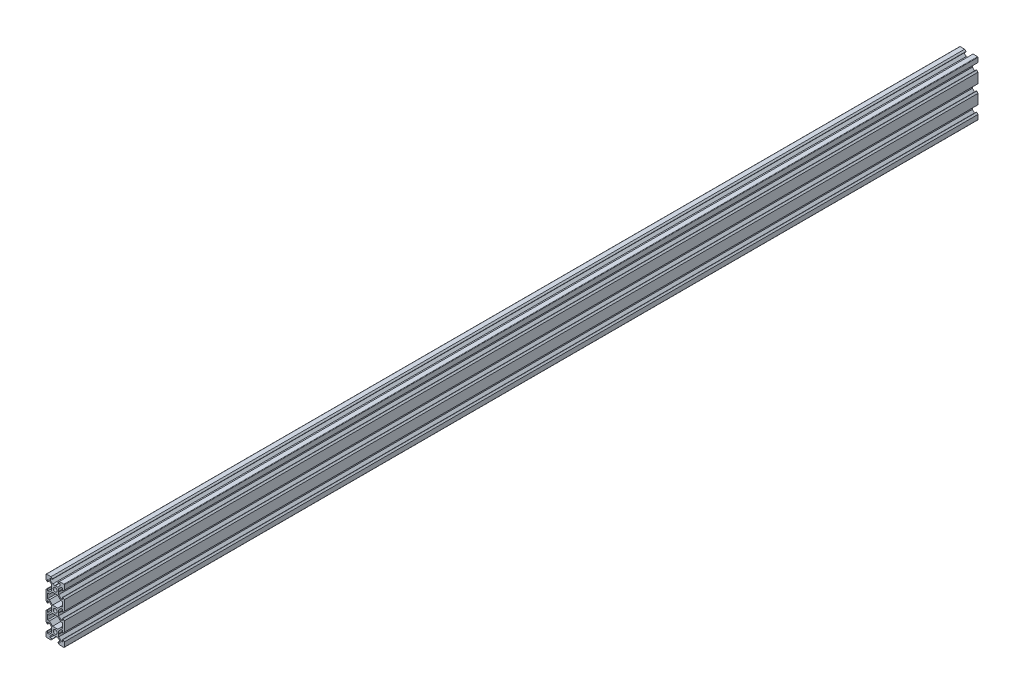
SolidWorks part; units mm, degrees
material "6061-T6 (SS)"
ref_plane "Front Plane" through (0, 0, 0) normal (0, 0, 1) x (1, 0, 0)
ref_plane "Top Plane" through (0, 0, 0) normal (0, 1, 0) x (1, 0, 0)
ref_plane "Right Plane" through (0, 0, 0) normal (1, 0, 0) x (0, 0, -1)
sketch "Sketch1" plane through (0, 0, 0) normal (0, 0, 1) x (1, 0, 0)
  line L0 (0, 0) -> (10, 0) construction
  line L1 (9.5, -30) -> (-9.5, -30)
  line L2 (10, -29.5) -> (10, 29.5)
  line L3 (9.5, 30) -> (-9.5, 30)
  line L4 (-10, -29.5) -> (-10, 29.5)
  line L5 (10, -30) -> (-10, 30) construction
  line L6 (10, 30) -> (-10, -30) construction
  circle A0 centre (0, 20) radius 2.1
  circle A1 centre (0, 0) radius 2.1
  circle A2 centre (0, -20) radius 2.1
  arc A3 (-9.5, -30) -> (-10, -29.5) centre (-9.5, -29.5) cw
  arc A4 (9.5, -30) -> (10, -29.5) centre (9.5, -29.5) ccw
  arc A5 (10, 29.5) -> (9.5, 30) centre (9.5, 29.5) ccw
  arc A6 (-9.5, 30) -> (-10, 29.5) centre (-9.5, 29.5) ccw
  point P0 (0, 0)
  line B0 (0, 20) -> (0, 30) construction
  line B1 (0, 23.69) -> (-0.21, 23.9)
  line B2 (-0.21, 23.9) -> (-2.8393, 23.9)
  line B3 (-2.8393, 23.9) -> (-5.5, 26.5607)
  line B4 (-5.5, 26.5607) -> (-5.5, 28.2)
  line B5 (-5.5, 28.2) -> (-3.125, 28.2)
  line B6 (-3.125, 28.2) -> (-3.125, 28.545)
  line B7 (-3.125, 28.545) -> (-4.58, 30)
  line B8 (-4.58, 30) -> (4.58, 30)
  line B9 (0, 20) -> (-5.9132, 25.9132) construction
  line B10 (3.125, 28.545) -> (4.58, 30)
  line B11 (3.125, 28.2) -> (3.125, 28.545)
  line B12 (5.5, 28.2) -> (3.125, 28.2)
  line B13 (5.5, 26.5607) -> (5.5, 28.2)
  line B14 (2.8393, 23.9) -> (5.5, 26.5607)
  line B15 (0.21, 23.9) -> (2.8393, 23.9)
  line B16 (0, 23.69) -> (0.21, 23.9)
  line B17 (0, 20) -> (-10, 20) construction
  line B18 (-3.69, 20) -> (-3.9, 19.79)
  line B19 (-3.9, 19.79) -> (-3.9, 17.1607)
  line B20 (-3.9, 17.1607) -> (-6.5607, 14.5)
  line B21 (-6.5607, 14.5) -> (-8.2, 14.5)
  line B22 (-8.2, 14.5) -> (-8.2, 16.875)
  line B23 (-8.2, 16.875) -> (-8.545, 16.875)
  line B24 (-8.545, 16.875) -> (-10, 15.42)
  line B25 (-10, 15.42) -> (-10, 24.58)
  line B26 (0, 20) -> (-5.9132, 14.0868) construction
  line B27 (-8.545, 23.125) -> (-10, 24.58)
  line B28 (-8.2, 23.125) -> (-8.545, 23.125)
  line B29 (-8.2, 25.5) -> (-8.2, 23.125)
  line B30 (-6.5607, 25.5) -> (-8.2, 25.5)
  line B31 (-3.9, 22.8393) -> (-6.5607, 25.5)
  line B32 (-3.9, 20.21) -> (-3.9, 22.8393)
  line B33 (-3.69, 20) -> (-3.9, 20.21)
  line B34 (0, 0) -> (-10, 0) construction
  line B35 (-3.69, 0) -> (-3.9, -0.21)
  line B36 (-3.9, -0.21) -> (-3.9, -2.8393)
  line B37 (-3.9, -2.8393) -> (-6.5607, -5.5)
  line B38 (-6.5607, -5.5) -> (-8.2, -5.5)
  line B39 (-8.2, -5.5) -> (-8.2, -3.125)
  line B40 (-8.2, -3.125) -> (-8.545, -3.125)
  line B41 (-8.545, -3.125) -> (-10, -4.58)
  line B42 (-10, -4.58) -> (-10, 4.58)
  line B43 (0, 0) -> (-5.9132, -5.9132) construction
  line B44 (-8.545, 3.125) -> (-10, 4.58)
  line B45 (-8.2, 3.125) -> (-8.545, 3.125)
  line B46 (-8.2, 5.5) -> (-8.2, 3.125)
  line B47 (-6.5607, 5.5) -> (-8.2, 5.5)
  line B48 (-3.9, 2.8393) -> (-6.5607, 5.5)
  line B49 (-3.9, 0.21) -> (-3.9, 2.8393)
  line B50 (-3.69, 0) -> (-3.9, 0.21)
  line B51 (0, -20) -> (-10, -20) construction
  line B52 (-3.69, -20) -> (-3.9, -20.21)
  line B53 (-3.9, -20.21) -> (-3.9, -22.8393)
  line B54 (-3.9, -22.8393) -> (-6.5607, -25.5)
  line B55 (-6.5607, -25.5) -> (-8.2, -25.5)
  line B56 (-8.2, -25.5) -> (-8.2, -23.125)
  line B57 (-8.2, -23.125) -> (-8.545, -23.125)
  line B58 (-8.545, -23.125) -> (-10, -24.58)
  line B59 (-10, -24.58) -> (-10, -15.42)
  line B60 (0, -20) -> (-5.9132, -25.9132) construction
  line B61 (-8.545, -16.875) -> (-10, -15.42)
  line B62 (-8.2, -16.875) -> (-8.545, -16.875)
  line B63 (-8.2, -14.5) -> (-8.2, -16.875)
  line B64 (-6.5607, -14.5) -> (-8.2, -14.5)
  line B65 (-3.9, -17.1607) -> (-6.5607, -14.5)
  line B66 (-3.9, -19.79) -> (-3.9, -17.1607)
  line B67 (-3.69, -20) -> (-3.9, -19.79)
  line B68 (0, -20) -> (0, -30) construction
  line B69 (0, -23.69) -> (0.21, -23.9)
  line B70 (0.21, -23.9) -> (2.8393, -23.9)
  line B71 (2.8393, -23.9) -> (5.5, -26.5607)
  line B72 (5.5, -26.5607) -> (5.5, -28.2)
  line B73 (5.5, -28.2) -> (3.125, -28.2)
  line B74 (3.125, -28.2) -> (3.125, -28.545)
  line B75 (3.125, -28.545) -> (4.58, -30)
  line B76 (4.58, -30) -> (-4.58, -30)
  line B77 (0, -20) -> (5.9132, -25.9132) construction
  line B78 (-3.125, -28.545) -> (-4.58, -30)
  line B79 (-3.125, -28.2) -> (-3.125, -28.545)
  line B80 (-5.5, -28.2) -> (-3.125, -28.2)
  line B81 (-5.5, -26.5607) -> (-5.5, -28.2)
  line B82 (-2.8393, -23.9) -> (-5.5, -26.5607)
  line B83 (-0.21, -23.9) -> (-2.8393, -23.9)
  line B84 (0, -23.69) -> (-0.21, -23.9)
  line B85 (0, -20) -> (10, -20) construction
  line B86 (3.69, -20) -> (3.9, -19.79)
  line B87 (3.9, -19.79) -> (3.9, -17.1607)
  line B88 (3.9, -17.1607) -> (6.5607, -14.5)
  line B89 (6.5607, -14.5) -> (8.2, -14.5)
  line B90 (8.2, -14.5) -> (8.2, -16.875)
  line B91 (8.2, -16.875) -> (8.545, -16.875)
  line B92 (8.545, -16.875) -> (10, -15.42)
  line B93 (10, -15.42) -> (10, -24.58)
  line B94 (0, -20) -> (5.9132, -14.0868) construction
  line B95 (8.545, -23.125) -> (10, -24.58)
  line B96 (8.2, -23.125) -> (8.545, -23.125)
  line B97 (8.2, -25.5) -> (8.2, -23.125)
  line B98 (6.5607, -25.5) -> (8.2, -25.5)
  line B99 (3.9, -22.8393) -> (6.5607, -25.5)
  line B100 (3.9, -20.21) -> (3.9, -22.8393)
  line B101 (3.69, -20) -> (3.9, -20.21)
  line B102 (0, 0) -> (10, 0) construction
  line B103 (3.69, 0) -> (3.9, 0.21)
  line B104 (3.9, 0.21) -> (3.9, 2.8393)
  line B105 (3.9, 2.8393) -> (6.5607, 5.5)
  line B106 (6.5607, 5.5) -> (8.2, 5.5)
  line B107 (8.2, 5.5) -> (8.2, 3.125)
  line B108 (8.2, 3.125) -> (8.545, 3.125)
  line B109 (8.545, 3.125) -> (10, 4.58)
  line B110 (10, 4.58) -> (10, -4.58)
  line B111 (0, 0) -> (5.9132, 5.9132) construction
  line B112 (8.545, -3.125) -> (10, -4.58)
  line B113 (8.2, -3.125) -> (8.545, -3.125)
  line B114 (8.2, -5.5) -> (8.2, -3.125)
  line B115 (6.5607, -5.5) -> (8.2, -5.5)
  line B116 (3.9, -2.8393) -> (6.5607, -5.5)
  line B117 (3.9, -0.21) -> (3.9, -2.8393)
  line B118 (3.69, 0) -> (3.9, -0.21)
  line B119 (0, 20) -> (10, 20) construction
  line B120 (3.69, 20) -> (3.9, 20.21)
  line B121 (3.9, 20.21) -> (3.9, 22.8393)
  line B122 (3.9, 22.8393) -> (6.5607, 25.5)
  line B123 (6.5607, 25.5) -> (8.2, 25.5)
  line B124 (8.2, 25.5) -> (8.2, 23.125)
  line B125 (8.2, 23.125) -> (8.545, 23.125)
  line B126 (8.545, 23.125) -> (10, 24.58)
  line B127 (10, 24.58) -> (10, 15.42)
  line B128 (0, 20) -> (5.9132, 25.9132) construction
  line B129 (8.545, 16.875) -> (10, 15.42)
  line B130 (8.2, 16.875) -> (8.545, 16.875)
  line B131 (8.2, 14.5) -> (8.2, 16.875)
  line B132 (6.5607, 14.5) -> (8.2, 14.5)
  line B133 (3.9, 17.1607) -> (6.5607, 14.5)
  line B134 (3.9, 19.79) -> (3.9, 17.1607)
  line B135 (3.69, 20) -> (3.9, 19.79)
  line B136 (-8.2, 7.3) -> (-8.2, 12.7)
  line B137 (-8.2, 12.7) -> (-6.2393, 12.7)
  line B138 (-6.2393, 12.7) -> (-2.8393, 16.1)
  line B139 (-2.8393, 16.1) -> (2.8393, 16.1)
  line B140 (0, 16.1) -> (0, 10) construction
  line B141 (0, 10) -> (-8.2, 10) construction
  line B142 (6.2393, 12.7) -> (2.8393, 16.1)
  line B143 (8.2, 12.7) -> (6.2393, 12.7)
  line B144 (8.2, 7.3) -> (8.2, 12.7)
  line B145 (8.2, 7.3) -> (6.2393, 7.3)
  line B146 (6.2393, 7.3) -> (2.8393, 3.9)
  line B147 (-2.8393, 3.9) -> (2.8393, 3.9)
  line B148 (-6.2393, 7.3) -> (-2.8393, 3.9)
  line B149 (-8.2, 7.3) -> (-6.2393, 7.3)
  line B150 (0, 16.1) -> (0, 20) construction
  line B151 (0, 20) -> (-5.0927, 14.9073) construction
  line B152 (-8.2, -12.7) -> (-8.2, -7.3)
  line B153 (-8.2, -7.3) -> (-6.2393, -7.3)
  line B154 (-6.2393, -7.3) -> (-2.8393, -3.9)
  line B155 (-2.8393, -3.9) -> (2.8393, -3.9)
  line B156 (0, -3.9) -> (0, -10) construction
  line B157 (0, -10) -> (-8.2, -10) construction
  line B158 (6.2393, -7.3) -> (2.8393, -3.9)
  line B159 (8.2, -7.3) -> (6.2393, -7.3)
  line B160 (8.2, -12.7) -> (8.2, -7.3)
  line B161 (8.2, -12.7) -> (6.2393, -12.7)
  line B162 (6.2393, -12.7) -> (2.8393, -16.1)
  line B163 (-2.8393, -16.1) -> (2.8393, -16.1)
  line B164 (-6.2393, -12.7) -> (-2.8393, -16.1)
  line B165 (-8.2, -12.7) -> (-6.2393, -12.7)
  line B166 (0, -3.9) -> (0, 0) construction
  line B167 (0, 0) -> (-5.0927, -5.0927) construction
  dimension "D3" = 4.2
  dimension "D5" = 0.5
  dimension "D1" = 20
  dimension "D2" = 60
  dimension "D4" = 40
sketch_block_instance "V Slot 1-4"
sketch_block "V Slot 1" parameters "D1"=10, "D2"=11, "D3"=4.3, "D4"=1.8, "D5"=0.21, "D6"=45, "D7"=9.16, "D8"=1.5, "D9"=6.25
sketch_block_instance "V Slot 1-5"
sketch_block_instance "V Slot 1-6"
sketch_block_instance "V Slot 1-7"
sketch_block_instance "V Slot 1-8"
sketch_block_instance "V Slot 1-9"
sketch_block_instance "V Slot 1-10"
sketch_block_instance "V Slot 1-11"
sketch_block_instance "Center Cutout 1-1"
sketch_block "Center Cutout 1" parameters "D1"=5.4, "D2"=12.2, "D3"=8.2, "D4"=45, "D5"=10, "D6"=1.5
sketch_block_instance "Center Cutout 1-2"
extrude "Boss-Extrude1" add sketch "Sketch1" along normal blind 1000 contours B135 B120 B121 B122 B123 B124 B125 B126 L2 A5 L3 B10 B11 B12 B13 B14 B15 B16 B1 B2 B3 B4 B5 B6 B7 A6 L4 B27 B28 B29 B30 B31 B32 B33 B18 B19 B20 B21 B22 B23 B24 B44 B45 B46 B47 B48 B49 B50 B35 region at (7.04, -29.3675, 0)
